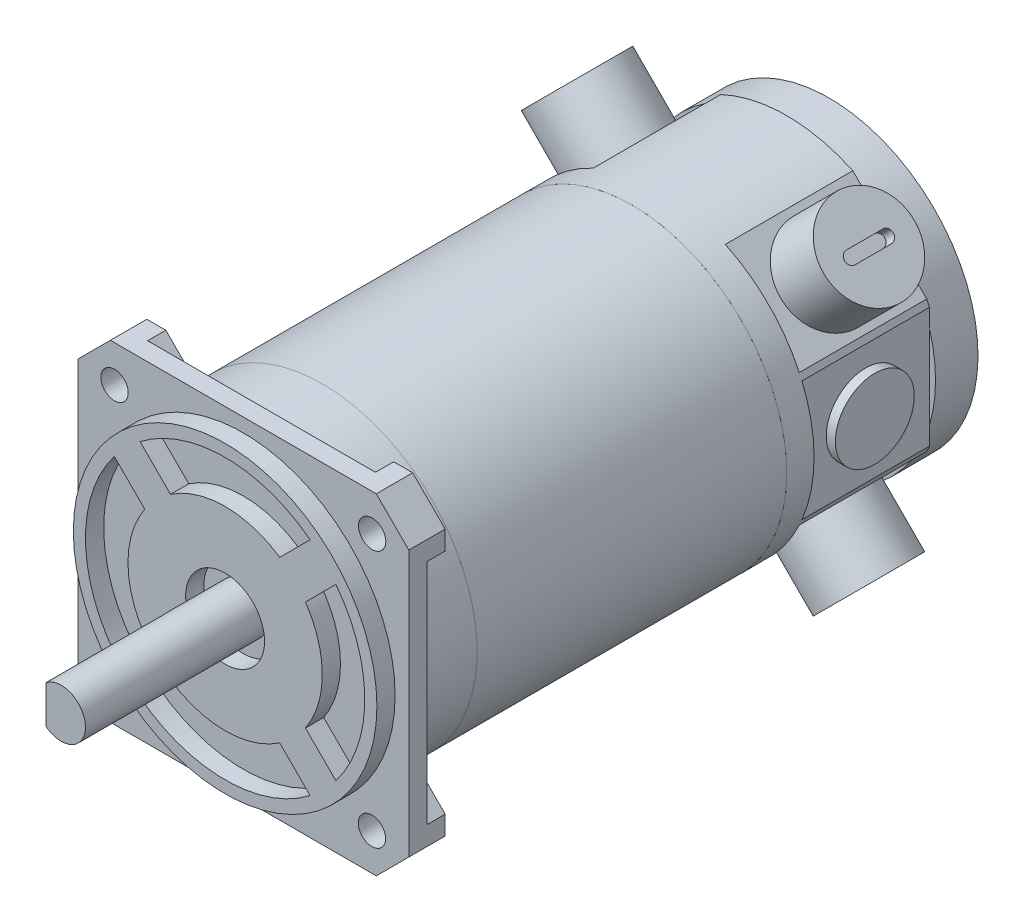
SolidWorks part; units mm, degrees
ref_plane "Front Plane" through (0, 0, 0) normal (0, 0, 1) x (1, 0, 0)
ref_plane "Top Plane" through (0, 0, 0) normal (0, 1, 0) x (1, 0, 0)
ref_plane "Right Plane" through (0, 0, 0) normal (1, 0, 0) x (0, 0, -1)
sketch "Sketch1" plane through (0, 0, 0) normal (0, 0, 1) x (1, 0, 0)
  line L1 (-27.25, -27.25) -> (27.25, -27.25)
  line L2 (-27.25, -27.25) -> (-27.25, 27.25)
  line L3 (-27.25, 27.25) -> (27.25, 27.25)
  line L4 (27.25, -27.25) -> (27.25, 27.25)
  line L5 (-27.25, -27.25) -> (27.25, 27.25) construction
  line L6 (-27.25, 27.25) -> (27.25, -27.25) construction
  point P0 (0, 0)
extrude "Boss-Extrude1" add sketch "Sketch1" along normal blind 3
sketch "Sketch2" plane through (0, 0, 3) normal (0, 0, 1) x (1, 0, 0)
  line L0 (-27.25, 27.25) -> (27.25, -27.25) construction
  line L1 (27.25, 27.25) -> (-27.25, -27.25) construction
  line L2 (-21.8939, 27.25) -> (-27.25, 21.8939)
  line L3 (-27.25, -21.8939) -> (-21.8939, -27.25)
  line L4 (21.8939, -27.25) -> (27.25, -27.25)
  line L5 (21.8939, 27.25) -> (27.25, 21.8939)
  line L6 (27.25, -21.8939) -> (21.8939, -27.25)
  line L7 (-51.822, 2.678) -> (2.678, -51.822) construction
  line L8 (2.678, 51.822) -> (-51.822, -2.678) construction
  line L9 (-2.678, 51.822) -> (51.822, -2.678) construction
  line L10 (27.25, -27.25) -> (27.25, 27.25)
  line L11 (27.25, 27.25) -> (-27.25, 27.25)
  line L12 (-27.25, 27.25) -> (-27.25, -27.25)
  line L13 (-27.25, -27.25) -> (27.25, -27.25)
  line L14 (27.25, -27.25) -> (27.25, -21.8939)
  line L15 (27.25, 27.25) -> (21.8939, 27.25)
  line L16 (-27.25, 27.25) -> (-27.25, 21.8939)
  line L17 (-27.25, -27.25) -> (-21.8939, -27.25)
  line L18 (-27.25, -21.8939) -> (-27.25, -27.25)
  line L19 (-21.8939, 27.25) -> (-27.25, 27.25)
  line L20 (27.25, 21.8939) -> (27.25, 27.25)
  line L21 (6.0368, 48.4632) -> (-48.4632, -6.0368) construction
  line L22 (-48.4632, 6.0368) -> (6.0368, -48.4632) construction
  line L23 (48.4632, 6.0368) -> (-6.0368, -48.4632) construction
  line L24 (-6.0368, 48.4632) -> (48.4632, -6.0368) construction
  line L25 (-13.2344, -8.9917) -> (-18.2458, -14.0032)
  line L30 (-8.9917, -13.2344) -> (-14.0032, -18.2458)
  line L31 (8.9917, -13.2344) -> (14.0032, -18.2458)
  line L32 (13.2344, -8.9917) -> (18.2458, -14.0032)
  line L39 (14.0032, 18.2458) -> (8.9917, 13.2344)
  line L40 (18.2458, 14.0032) -> (13.2344, 8.9917)
  line L41 (-18.2458, 14.0032) -> (-13.2344, 8.9917)
  line L42 (-14.0032, 18.2458) -> (-8.9917, 13.2344)
  circle A0 centre (0, 0) radius 25
  circle A1 centre (0, 0) radius 23
  circle A2 centre (0, 0) radius 16
  circle A3 centre (0, 0) radius 6.5
  circle A4 centre (21.1758, -21.1758) radius 2.25
  circle A5 centre (21.2132, 21.2132) radius 2.25
  circle A6 centre (-21.2132, 21.2132) radius 2.25
  circle A7 centre (-21.2132, -21.2132) radius 2.25
  point P12 (51.822, 2.678)
  point P13 (-2.678, -51.822)
  point P29 (-29.3713, 25.1287)
  point P30 (25.1287, -29.3713)
  point P31 (25.1287, 29.3713)
  point P32 (-29.3713, -25.1287)
  point P33 (-25.1287, 29.3713)
  point P34 (29.3713, -25.1287)
  point P35 (29.3713, 25.1287)
  point P36 (-25.1287, -29.3713)
  line M5 (27.25, -27.25) -> (27.25, 27.25)
  line M6 (27.25, 27.25) -> (-27.25, 27.25)
  line M7 (-27.25, 27.25) -> (-27.25, -27.25)
  line M8 (-27.25, -27.25) -> (27.25, -27.25)
  dimension "D4" = 30
  dimension "D1" = 34.75
  dimension "D2" = 34.75
  dimension "D3" = 0
  dimension "D5" = 30
extrude "Cut-Extrude1" cut sketch "Sketch2" against normal up to surface (3 mm away) contours L2 M6 M7 | L5 M6 M5 | L3 M7 M8 | L6 M5 M8 | A7 | A4 | A5 | A6 region at (-25.4646, 25.4646, 3) region at (25.4646, 25.4646, 3) region at (-25.4646, -25.4646, 3) region at (25.4646, -25.4646, 3) region at (21.1758, -21.1758, 3) region at (21.2132, 21.2132, 3) region at (-21.2132, 21.2132, 3) region at (-21.2132, -21.2132, 3) up to face at (0, 0, 0)
extrude "Boss-Extrude2" add sketch "Sketch2<3>" along normal blind 3 contours A0 A1 | A2 A3 | A2 L40 A1 L39 | A2 L31 A1 L32 | A2 L25 A1 L30 | A2 L42 A1 L41 region at (-13.732, -13.732, 3) region at (-15.5475, 0, 3) region at (-13.732, 13.732, 3) region at (13.732, -13.732, 3) region at (13.732, 13.732, 3) region at (-24.2929, 0, 3)
sketch "Sketch2<3>" plane through (0, 0, 3) normal (0, 0, 1) x (1, 0, 0) same geometry as "Sketch2"
sketch "Sketch3" plane through (0, 0, 3) normal (0, 0, 1) x (1, 0, 0)
  circle A0 centre (0, 0) radius 4
extrude "Boss-Extrude3" add sketch "Sketch3" along normal blind 30 separate body
sketch "Sketch4" plane through (0, 0, 33) normal (0, 0, 1) x (1, 0, 0)
  line L0 (0, 4) -> (0, -4) construction
  line L1 (-2.5, 3.1225) -> (-2.5, -3.1225)
  line L3 (-2.5, 4) -> (-2.5, -4) construction
  circle A1 centre (0, 0) radius 4
  arc A2 (-2.5, 3.1225) -> (-2.5, -3.1225) centre (0, 0) ccw
  dimension "D2" = 2.5
  dimension "D1" = 0
extrude "Cut-Extrude2" cut sketch "Sketch4" against normal blind 20
sketch "Sketch5" plane through (0, 0, 0) normal (0, 0, -1) x (-1, 0, 0)
  line L0 (24.572, 24.572) -> (-24.572, -24.572) construction
  line L1 (21.8939, 27.25) -> (27.25, 21.8939) construction
  line L2 (-27.25, -21.8939) -> (-21.8939, -27.25) construction
  line L3 (-24.572, 24.572) -> (24.572, -24.572) construction
  line L4 (-21.8939, 27.25) -> (-27.25, 21.8939) construction
  line L5 (27.25, -21.8939) -> (21.8939, -27.25) construction
  line L6 (18.7647, 27.25) -> (13.2823, 21.7676)
  line L7 (-27.25, 18.7647) -> (-21.7676, 13.2823)
  line L8 (27.25, 18.7647) -> (21.7676, 13.2823)
  line L9 (-18.7647, 27.25) -> (-13.2823, 21.7676)
  line L10 (27.25, 18.7647) -> (27.25, 21.8939)
  line L11 (-28.8146, 20.3293) -> (20.3293, -28.8146) construction
  line L12 (-20.3293, 28.8146) -> (28.8146, -20.3293) construction
  line L13 (18.7647, -27.25) -> (21.8939, -27.25)
  line L14 (-27.25, -18.7647) -> (-27.25, -21.8939)
  line L15 (28.8146, 20.3293) -> (-20.3293, -28.8146) construction
  line L16 (20.3293, 28.8146) -> (-28.8146, -20.3293) construction
  line L17 (-21.7676, -13.2823) -> (-27.25, -18.7647)
  line L18 (-27.25, -21.8939) -> (-21.8939, -27.25)
  line L19 (-21.8939, -27.25) -> (21.8939, -27.25)
  line L20 (21.8939, -27.25) -> (27.25, -21.8939)
  line L21 (27.25, -21.8939) -> (27.25, 21.8939)
  line L22 (27.25, 21.8939) -> (21.8939, 27.25)
  line L23 (21.8939, 27.25) -> (-21.8939, 27.25)
  line L24 (-21.8939, 27.25) -> (-27.25, 21.8939)
  line L25 (-27.25, 21.8939) -> (-27.25, -21.8939)
  line L26 (-27.25, -21.8939) -> (-21.8939, -27.25)
  line L27 (-21.8939, -27.25) -> (-18.7647, -27.25)
  line L28 (21.8939, -27.25) -> (27.25, -21.8939)
  line L29 (27.25, -21.8939) -> (27.25, -18.7647)
  line L30 (27.25, 21.8939) -> (21.8939, 27.25)
  line L31 (21.8939, 27.25) -> (18.7647, 27.25)
  line L32 (-21.8939, 27.25) -> (-27.25, 21.8939)
  line L33 (-27.25, 21.8939) -> (-27.25, 18.7647)
  line L34 (-13.2823, -21.7676) -> (-18.7647, -27.25)
  line L35 (13.2823, -21.7676) -> (18.7647, -27.25)
  line L36 (21.7676, -13.2823) -> (27.25, -18.7647)
  line L41 (-18.7647, 27.25) -> (-21.8939, 27.25)
  circle A0 centre (0, 0) radius 25.5
  circle A1 centre (21.2132, 21.2132) radius 2.25 construction
  circle A2 centre (-21.2132, 21.2132) radius 2.25 construction
  circle A3 centre (-21.1758, -21.1758) radius 2.25 construction
  circle A4 centre (21.2132, -21.2132) radius 2.25 construction
  circle A5 centre (21.2132, 21.2132) radius 2.25
  circle A6 centre (-21.2132, 21.2132) radius 2.25
  circle A7 centre (-21.1758, -21.1758) radius 2.25
  circle A8 centre (21.2132, -21.2132) radius 2.25
  circle A9 centre (0, 0) radius 18.5
  circle M9 centre (21.2132, 21.2132) radius 2.25
  circle M10 centre (-21.2132, 21.2132) radius 2.25
  circle M11 centre (-21.1758, -21.1758) radius 2.25
  circle M12 centre (21.2132, -21.2132) radius 2.25
  line M13 (-27.25, -21.8939) -> (-21.8939, -27.25)
  line M14 (-21.8939, -27.25) -> (21.8939, -27.25)
  line M15 (21.8939, -27.25) -> (27.25, -21.8939)
  line M16 (27.25, -21.8939) -> (27.25, 21.8939)
  line M17 (27.25, 21.8939) -> (21.8939, 27.25)
  line M18 (21.8939, 27.25) -> (-21.8939, 27.25)
  line M19 (-21.8939, 27.25) -> (-27.25, 21.8939)
  line M20 (-27.25, 21.8939) -> (-27.25, -21.8939)
  dimension "D1" = 6
  dimension "D4" = 7
  dimension "D2" = 6
  dimension "D3" = 0
extrude "Boss-Extrude4" add sketch "Sketch5" along normal blind 3 contours A0 L8 L6 M16 M17 M18 M9 | A0 L9 L7 M18 M19 M20 M10 | A0 L17 L34 M20 M13 M14 M11 | A0 L35 L36 M14 M15 M16 M12 region at (-20.3293, 27.0525, 0) region at (16.1632, 24.3691, 0) region at (-27.0525, -20.3293, 0) region at (18.1709, -18.1709, 0)
extrude "Boss-Extrude5" add sketch "Sketch5<3>" along normal blind 10 contours A0 region at (-17.5212, 17.5212, 0)
sketch "Sketch5<3>" plane through (0, 0, 0) normal (0, 0, -1) x (-1, 0, 0) same geometry as "Sketch5"
sketch "Sketch6" plane through (0, 0, -10) normal (0, 0, -1) x (-1, 0, 0)
  circle A0 centre (0, 0) radius 18.5 construction
  circle A1 centre (0, 0) radius 25.5
  circle A2 centre (0, 0) radius 25.5
  circle A3 centre (0, 0) radius 18.5
  dimension "D1" = 0
extrude "Boss-Extrude6" add sketch "Sketch6" along normal blind 51 separate body
sketch "Sketch7" plane through (0, 0, -61) normal (0, 0, -1) x (-1, 0, 0)
  line L0 (27.25, 21.8939) -> (21.8939, 27.25) construction
  line L1 (-27.25, -21.8939) -> (-21.8939, -27.25) construction
  line L2 (21.8939, -27.25) -> (27.25, -21.8939) construction
  line L3 (-21.8939, 27.25) -> (-27.25, 21.8939) construction
  line L4 (27.25, 21.8939) -> (21.8939, 27.25) construction
  line L5 (-27.25, -21.8939) -> (-21.8939, -27.25) construction
  line L6 (21.8939, -27.25) -> (27.25, -21.8939) construction
  line L7 (-21.8939, 27.25) -> (-27.25, 21.8939) construction
  line L8 (24.572, 24.572) -> (-24.572, -24.572) construction
  line L9 (-24.572, 24.572) -> (24.572, -24.572) construction
  line L10 (0, 25.5) -> (0, -25.5) construction
  line L11 (-23.5, 25.5) -> (-23.5, 23.5)
  line L12 (23.5, 25.5) -> (23.5, 23.5)
  line L13 (-23.5, -23.5) -> (-23.5, -25.5)
  line L14 (-23.5, 9.8995) -> (-23.5, -9.8995)
  line L15 (-10.8775, 23.0636) -> (-23.0636, 10.8775)
  line L16 (-23.5, 25.5) -> (-23.5, -25.5) construction
  line L17 (10.8775, 23.0636) -> (23.0636, 10.8775)
  line L18 (23.5, 9.8995) -> (23.5, -9.8995)
  line L19 (23.5, -23.5) -> (23.5, -25.5)
  line L20 (23.0636, -10.8775) -> (10.8775, -23.0636)
  line L21 (23.5, 25.5) -> (23.5, -25.5) construction
  line L24 (-23.0636, -10.8775) -> (-10.8775, -23.0636)
  circle A0 centre (0, 0) radius 25.5 construction
  circle A1 centre (0, 0) radius 25.5
  circle A2 centre (0, 0) radius 18.5 construction
  circle A3 centre (0, 0) radius 18.5
  point P15 (-41.5425, 7.6014)
  point P16 (7.6014, -41.5425)
  point P17 (7.6014, 41.5425)
  point P18 (-41.5425, -7.6014)
  point P19 (-7.6014, 41.5425)
  point P20 (41.5425, -7.6014)
  point P21 (41.5425, 7.6014)
  point P22 (-7.6014, -41.5425)
  circle M5 centre (0, 0) radius 25.5
  circle M6 centre (0, 0) radius 18.5
  dimension "D1" = 23.5
  dimension "D2" = 23.5
extrude "Boss-Extrude7" add sketch "Sketch7" along normal blind 4.5 separate body contours L14 M5 | L15 M5 | L17 M5 | L18 M5 | L20 M5 | L24 M5 | L24 L20 L18 L17 L15 L14 M5 M6 region at (22.6536, 10.1082, -61) region at (24.3028, 0, -61) region at (17.3959, 17.3959, -61) region at (17.3959, -17.3959, -61) region at (-17.3959, 17.3959, -61) region at (-17.3959, -17.3959, -61) region at (-24.3028, 0, -61)
extrude "Boss-Extrude8" add sketch "Sketch7<3>" along normal blind 21 from surface contours L24 L20 L18 L17 L15 L14 M5 M6 region at (22.6536, 10.1082, -61) starting at face at (-25.5, 0, -65.5)
sketch "Sketch7<3>" plane through (0, 0, -61) normal (0, 0, -1) x (-1, 0, 0) same geometry as "Sketch7"
sketch "Sketch8" plane through (0, 0, -86.5) normal (0, 0, -1) x (-1, 0, 0)
  circle A0 centre (0, 0) radius 24.5
extrude "Boss-Extrude9" add sketch "Sketch8" along normal blind 7
sketch "Sketch9" plane through (0, 0, -93.5) normal (0, 0, -1) x (-1, 0, 0)
  circle A0 centre (0, 0) radius 12.5
extrude "Boss-Extrude10" add sketch "Sketch9" along normal blind 8
sketch "Sketch10" plane through (0, 0, -101.5) normal (0, 0, -1) x (-1, 0, 0)
  circle A0 centre (0, 0) radius 6.5
  circle A1 centre (0, 0) radius 3
extrude "Cut-Extrude3" cut sketch "Sketch10" against normal blind 3
extrude "Boss-Extrude11" add sketch "Sketch10<2>" along normal blind 4 contours A1 region at (0, 0, -101.5)
sketch "Sketch10<2>" plane through (0, 0, -101.5) normal (0, 0, -1) x (-1, 0, 0) same geometry as "Sketch10"
sketch "Sketch11" plane through (16.9706, -16.9706, 0) normal (0.7071, -0.7071, 0) x (0, 0, -1)
  circle A0 centre (76, 0) radius 7.5
extrude "Boss-Extrude12" add sketch "Sketch11" along normal blind 10 separate body
sketch "Sketch12" plane through (24.0416, -24.0416, 0) normal (0.7071, -0.7071, 0) x (0, 0, -1)
  line L0 (68.5, 0) -> (83.5, 0) construction
  line L1 (79, 0) -> (73, 0) construction
  line L3 (79, -1) -> (73, -1)
  line L4 (79, 1) -> (73, 1)
  circle A0 centre (76, 0) radius 7.5 construction
  arc A1 (79, -1) -> (79, 1) centre (79, 0) ccw
  arc A2 (73, 1) -> (73, -1) centre (73, 0) ccw
  point P9 (76, 0)
extrude "Cut-Extrude4" cut sketch "Sketch12" against normal blind 2
pattern_circular "CirPattern2" count 4 over 360 about axis through (0, 0, -65.5) along (0, 0, 1) of "Boss-Extrude12", "Cut-Extrude4"
sketch "Sketch13" plane through (-23.5, 0, 0) normal (-1, 0, 0) x (0, 0, 1)
  circle A0 centre (-76, 0) radius 8
extrude "Boss-Extrude13" add sketch "Sketch13" along normal blind 2 separate body
sketch "Sketch14" plane through (23.5, 0, 0) normal (1, 0, 0) x (0, 0, -1)
  circle A0 centre (76, 0) radius 6.5
extrude "Boss-Extrude14" add sketch "Sketch14" along normal blind 1.5 separate body
sketch "Sketch15" plane through (0, 0, 6) normal (0, 0, 1) x (1, 0, 0)
  line L0 (-21.8939, -27.25) -> (21.8939, -27.25) construction
  line L1 (-29.3449, -18.7383) -> (-18.7383, -29.3449) construction
  line L2 (21.8939, 27.25) -> (-21.8939, 27.25) construction
  line L3 (-27.25, 21.8939) -> (-27.25, -21.8939) construction
  line L4 (27.25, -21.8939) -> (27.25, 21.8939) construction
  line L5 (-21.8939, -27.25) -> (21.8939, -27.25)
  line L6 (-29.3449, -18.7383) -> (-18.7383, -29.3449)
  line L7 (21.8939, 27.25) -> (-21.8939, 27.25)
  line L8 (-27.25, 21.8939) -> (-27.25, -21.8939)
  line L9 (27.25, -21.8939) -> (27.25, 21.8939)
  circle A0 centre (-21.2132, 21.2132) radius 2.25 construction
  circle A1 centre (21.2132, 21.2132) radius 2.25 construction
  circle A2 centre (-21.2132, -21.2132) radius 2.25 construction
  circle A3 centre (21.1758, -21.1758) radius 2.25 construction
  circle A4 centre (-21.2132, 21.2132) radius 2.25
  circle A5 centre (21.2132, 21.2132) radius 2.25
  circle A6 centre (-21.2132, -21.2132) radius 2.25
  circle A7 centre (21.1758, -21.1758) radius 2.25
  circle A8 centre (0, 0) radius 6.5 construction
  circle A9 centre (0, 0) radius 6.5
